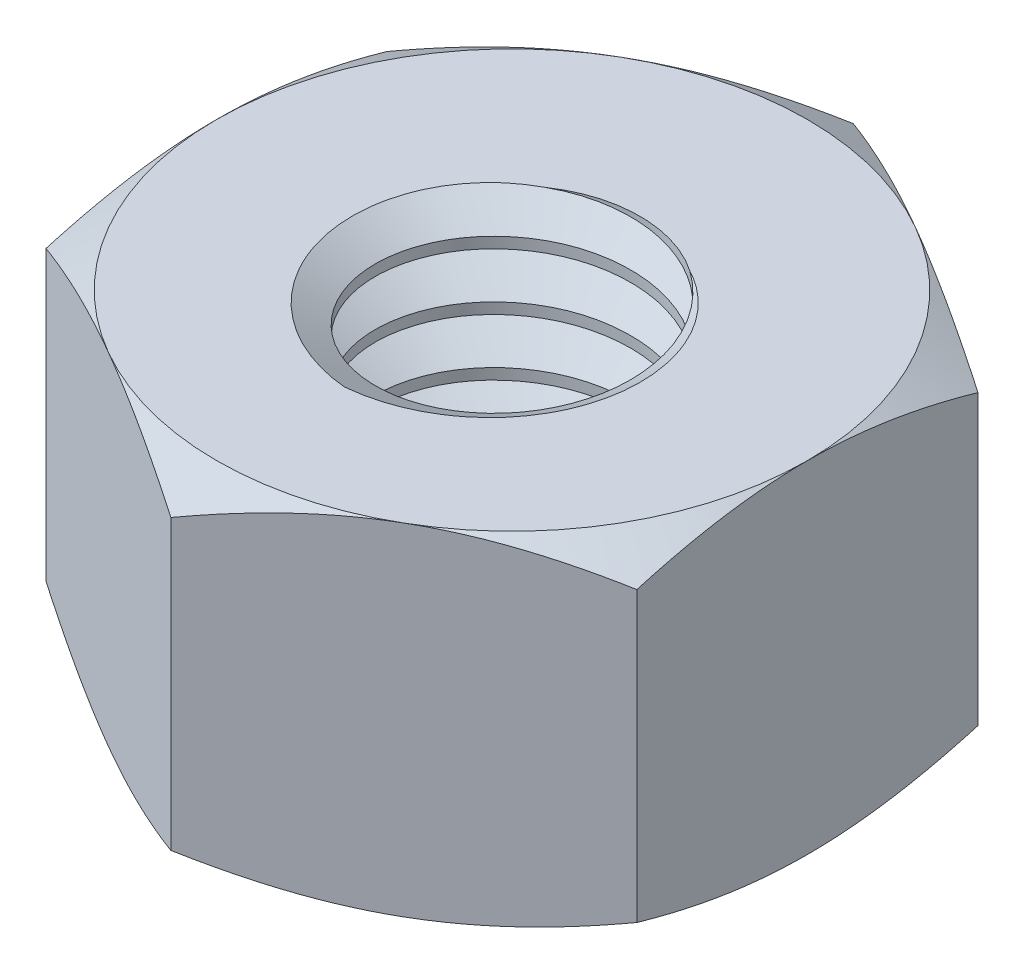
SolidWorks part; units mm, degrees
material "Plain Carbon Steel"
ref_plane "Front Plane" through (0, 0, 0) normal (0, 0, 1) x (1, 0, 0)
ref_plane "Top Plane" through (0, 0, 0) normal (0, 1, 0) x (1, 0, 0)
ref_plane "Right Plane" through (0, 0, 0) normal (1, 0, 0) x (0, 0, -1)
sketch "Sketch1" plane through (0, 0, 0) normal (0, 1, 0) x (1, 0, 0)
  line L1 (0, 12) -> (-10.3923, 6)
  line L2 (-10.3923, 6) -> (-10.3923, -6)
  line L3 (-10.3923, -6) -> (0, -12)
  line L4 (0, -12) -> (10.3923, -6)
  line L5 (10.3923, -6) -> (10.3923, 6)
  line L6 (10.3923, 6) -> (0, 12)
  circle A0 centre (0, 0) radius 10.3923 construction
  circle A1 centre (0, 0) radius 4.5
  dimension "D2" = 9
  dimension "D1" = 12
extrude "Boss-Extrude1" add sketch "Sketch1" along normal mid plane 12
sketch "Sketch2" plane through (0, 6, 0) normal (0, 1, 0) x (1, 0, 0)
  circle A0 centre (0, 0) radius 10.3923
extrude "Cut-Extrude1" cut sketch "Sketch2" against normal blind 12 draft 60 flip side to cut
mirror "Mirror1" about plane through (0, 0, 0) normal (0, 1, 0) of "Cut-Extrude1"
sketch "Sketch3" plane through (0, 6, 0) normal (0, 1, 0) x (1, 0, 0)
  circle A0 centre (0, 0) radius 4.5 construction
  circle A1 centre (0, 0) radius 4.5
curve "Helix/Spiral1" pitch 2 height 12 radius 4.5 centre (0, 6, 0) axis (0, -1, 0) start towards (0, 0, 1)
sketch "Sketch5" plane through (0, 0, 0) normal (1, 0, 0) x (0, 0, -1)
  line L0 (0, 6) -> (-9, 6) construction
  line L1 (-5.9, 6) -> (-3.8, 4.7876)
  line L2 (-3.8, 4.7876) -> (-3.8, 7.2124)
  line L3 (-3.8, 7.2124) -> (-5.9, 6)
  circle A0 centre (-4.5, 6) radius 0.7 construction
  dimension "D1" = 1.4
sweep "Cut-Sweep1" cut profiles "Sketch5" path "Helix/Spiral1" align with end faces yes
